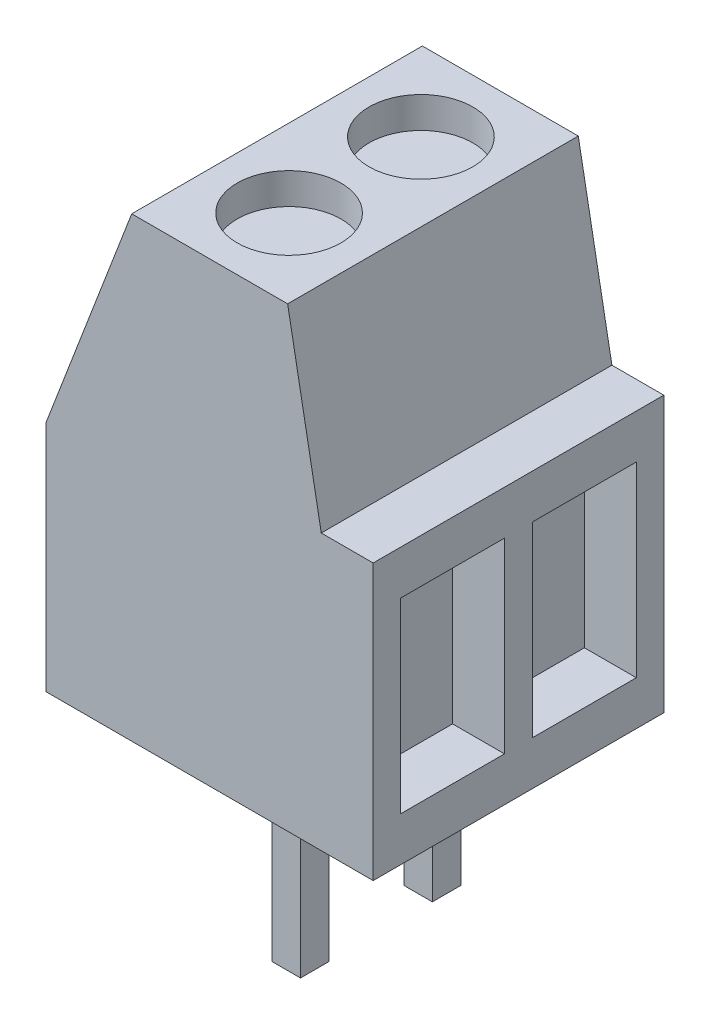
SolidWorks part; units mm, degrees
ref_plane "Front Plane" through (0, 0, 0) normal (0, 0, 1) x (1, 0, 0)
ref_plane "Top Plane" through (0, 0, 0) normal (0, 1, 0) x (1, 0, 0)
ref_plane "Right Plane" through (0, 0, 0) normal (1, 0, 0) x (0, 0, -1)
sketch "Sketch2" plane through (0, 0, 0) normal (0, 0, 1) x (1, 0, 0)
  line L1 (6.3, 5.3) -> (5.3, 5.3)
  line L5 (6.3, 5.3) -> (6.3, 0)
  line L6 (6.3, 0) -> (0, 0)
  line L7 (5.3, 5.3) -> (4.6521, 8.8)
  line L8 (4.6521, 8.8) -> (1.6479, 8.8)
  line L9 (1.6479, 8.8) -> (0, 4.5)
  line L10 (0, 4.5) -> (0, 0)
  line L11 (3.15, 8.8) -> (3.15, 0) construction
  dimension "D1" = 8.8
  dimension "D2" = 6.3
  dimension "D3" = 1
  dimension "D4" = 5.3
  dimension "D5" = 3.0042
  dimension "D6" = 4.5
extrude "Boss-Extrude1" add sketch "Sketch2" against normal blind 5.6
sketch "Sketch3" plane through (0, 8.8, 0) normal (0, 1, 0) x (1, 0, 0)
  line L0 (3.15, 56) -> (3.15, 0) construction
  line L1 (1.6479, 0) -> (4.6521, 0) construction
  line L3 (3.15, 1.53) -> (3.15, 4.07) construction
  circle A0 centre (3.15, 1.53) radius 1
  circle A1 centre (3.15, 4.07) radius 1
  point P2 (3.15, 0)
  dimension "D4" = 2
  dimension "D2" = 2.54
  dimension "D3" = 1.53
  dimension "D1" = 2
extrude "Cut-Extrude1" cut sketch "Sketch3" against normal blind 0.6
sketch "Sketch4" plane through (6.3, 0, 0) normal (1, 0, 0) x (0, 0, -1)
  line L0 (3.07, 0.85) -> (5.07, 0.85)
  line L1 (0.53, 0.85) -> (2.53, 0.85)
  line L2 (0.53, 0.85) -> (0.53, 4.45)
  line L3 (0.53, 4.45) -> (2.53, 4.45)
  line L4 (2.53, 0.85) -> (2.53, 4.45)
  line L5 (3.07, 0.85) -> (3.07, 4.45)
  line L6 (3.07, 4.45) -> (5.07, 4.45)
  line L7 (5.07, 0.85) -> (5.07, 4.45)
  line L64 (0.53, 0.85) -> (3.07, 0.85) construction
  line L65 (1.53, 2.65) -> (0, 2.65) construction
  line L66 (0, 0) -> (0, 5.3) construction
  line L67 (1.53, 4.45) -> (1.53, 0.85) construction
  dimension "D1" = 2
  dimension "D2" = 3.6
  dimension "D4" = 2.54
  dimension "D5" = 1.53
  dimension "D3" = 2
extrude "Cut-Extrude2" cut sketch "Sketch4" against normal blind 1
sketch "Sketch5" plane through (0, 0, 0) normal (0, -1, 0) x (1, 0, 0)
  line L0 (3.15, 0) -> (3.15, -5.6) construction
  line L1 (0, 0) -> (6.3, 0) construction
  line L3 (3.15, -1.475) -> (3.15, -2.025) construction
  line L4 (2.875, -1.475) -> (3.425, -1.475)
  line L5 (2.875, -1.475) -> (2.875, -2.025)
  line L6 (2.875, -2.025) -> (3.425, -2.025)
  line L7 (3.425, -1.475) -> (3.425, -2.025)
  line L8 (3.425, -1.75) -> (2.875, -1.75) construction
  line L14 (3.425, -4.29) -> (2.875, -4.29) construction
  line L15 (2.875, -4.015) -> (2.875, -4.565)
  line L16 (2.875, -4.015) -> (3.425, -4.015)
  line L21 (3.425, -4.015) -> (3.425, -4.565)
  line L22 (2.875, -4.565) -> (3.425, -4.565)
  line L23 (0, -5.6) -> (6.3, -5.6) construction
  line L145 (3.425, -1.75) -> (3.425, -4.29) construction
  point P4 (3.15, 0)
  point P16 (3.15, -1.75)
  point P110 (3.15, -4.29)
  dimension "D2" = 0.55
  dimension "D3" = 1.75
  dimension "D5" = 2.54
  dimension "D4" = 2
extrude "Boss-Extrude2" add sketch "Sketch5" along normal blind 3.8 separate body
ref_axis "Axis1" through (3.15, 0, -1.75) along (0, -1, 0)
ref_axis "Axis2" through (3.15, 0, -4.29) along (0, -1, 0)
ref_plane "mid-plane" through (0, 0, -2.8) normal (0, 0, 1) x (1, 0, 0)
